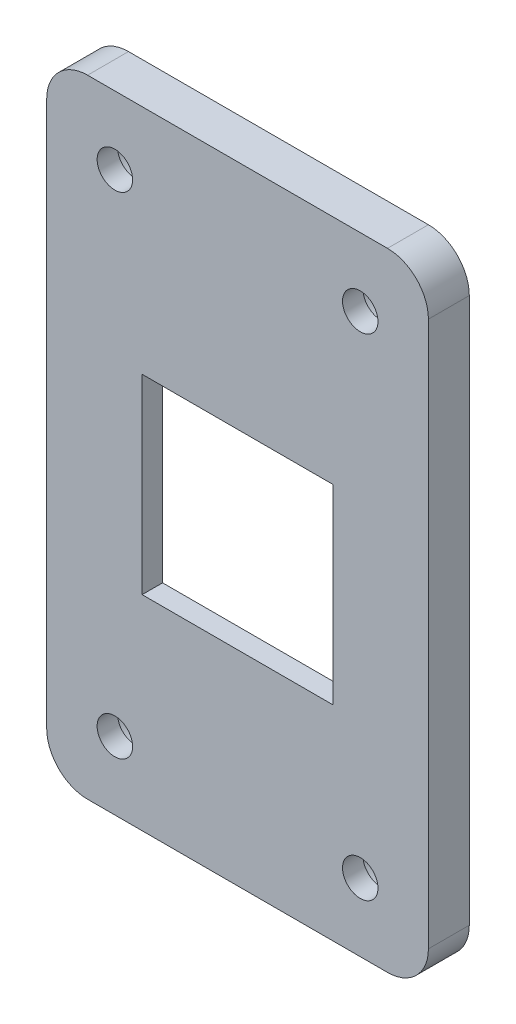
SolidWorks part; units mm, degrees
ref_plane "Front Plane" through (0, 0, 0) normal (1, 0, 0) x (0, 1, 0)
ref_plane "Top Plane" through (0, 0, 0) normal (0, 0, 1) x (0, 1, 0)
ref_plane "Right Plane" through (0, 0, 0) normal (0, 1, 0) x (-1, 0, 0)
sketch "Sketch2" plane through (0, 0, 0) normal (0, 0, 1) x (0, 1, 0)
  line L0 (-11, 10) -> (9, 10)
  line L1 (18, 9) -> (-18, 9) construction
  line L2 (18, 9) -> (18, -9) construction
  line L3 (18, -9) -> (-18, -9) construction
  line L4 (-18, 9) -> (-18, -9) construction
  line L5 (18, 9) -> (-18, -9) construction
  line L6 (18, -9) -> (-18, 9) construction
  line L7 (23, 14) -> (-23, 14)
  line L8 (23, 14) -> (23, -14)
  line L9 (23, -14) -> (-23, -14)
  line L10 (-23, 14) -> (-23, -14)
  line L11 (23, 14) -> (-23, -14) construction
  line L12 (23, -14) -> (-23, 14) construction
  line L13 (-8, 7) -> (6, 7)
  line L14 (-8, 7) -> (-8, -7)
  line L15 (-8, -7) -> (6, -7)
  line L16 (6, 7) -> (6, -7)
  line L17 (-8, 7) -> (6, -7) construction
  line L18 (-8, -7) -> (6, 7) construction
  line L19 (9, 10) -> (9, -10)
  line L20 (-11, -10) -> (9, -10)
  line L21 (-11, 10) -> (-11, -10)
  line L22 (23, 0) -> (-23, 0) construction
  circle A0 centre (-18, 9) radius 2.5
  circle A1 centre (18, 9) radius 2.5
  circle A2 centre (18, -9) radius 2.5
  circle A3 centre (-18, -9) radius 2.5
  point P0 (0, 0)
  point P6 (0, 0)
  point P16 (0, 0)
  point P26 (-1, 0)
  point P27 (0, 0)
  point P28 (0, 0)
  dimension "D5" = 5
  dimension "D1" = 36
  dimension "D2" = 18
  dimension "D3" = 5
  dimension "D4" = 5
  dimension "D6" = 14
  dimension "D8" = 1
  dimension "D7" = 3
extrude "Boss-Extrude1" add sketch "Sketch2" along normal blind 3 contours A3 | L7 L10 L9 L8 A3 A2 A1 A0 | A0 | A1 | A2 | L0 L21 L20 L19 L13 L16 L15 L14 region at (-9.7172, -1, 0) region at (0, 22.4615, 0) region at (-9, -18, 0) region at (-9, 18, 0) region at (9, 18, 0) region at (9, -18, 0)
hole_wizard "Ø2.6 (2.6) Diameter Hole1" positions "Sketch4" profile "Sketch5" hole size "Ø2.6" standard "ANSI Metric" end condition through all
sketch "Sketch4" plane through (0, 0, 0) normal (0, 0, -1) x (-1, 0, 0)
  point P0 (-9, -18)
  point P3 (9, -18)
  point P6 (-9, 18)
  point P9 (9, 18)
sketch "Sketch5" plane through (9, -18, 0) normal (1, 0, 0) x (0, 1, 0)
  line L0 (0, 0) -> (0, 3)
  line L1 (0, 3) -> (1.3, 3)
  line L2 (1.3, 3) -> (1.3, 0)
  line L5 (1.3, 0) -> (0, 0)
  line L11 (0, -6.35) -> (0, 107.95) construction
  dimension "Thru Hole Dia." = 2.6
  dimension "Thru Hole Depth" = 3
extrude "Cut-Extrude2" cut sketch "Sketch2<6>" along normal blind 1.5 contours A3 | A0 | A1 | A2 | L0 L19 L20 L21 region at (-9, -18, 0) region at (-9, 18, 0) region at (9, 18, 0) region at (9, -18, 0)
sketch "Sketch2<6>" plane through (0, 0, 0) normal (0, 0, 1) x (0, 1, 0) same geometry as "Sketch2"
fillet "Fillet1" radius 3 4 edges at (14, 23, 1.5) (14, -23, 1.5) (-14, -23, 1.5) (-14, 23, 1.5)
sketch "Sketch6" plane through (0, 0, 0) normal (0, 0, -1) x (1, 0, 0)
  line L0 (0, 15) -> (0, 13) construction
  line L1 (0.5, 15) -> (0.5, 13)
  line L2 (-0.5, 15) -> (-0.5, 13)
  line L3 (-10, 11) -> (10, 11) construction
  arc A0 (0.5, 15) -> (-0.5, 15) centre (0, 15) ccw
  arc A1 (-0.5, 13) -> (0.5, 13) centre (0, 13) ccw
  point P3 (0, 14)
  dimension "D1" = 1
  dimension "D2" = 2
  dimension "D3" = 3
extrude "Cut-Extrude3" cut sketch "Sketch6" against normal blind 0.4
equation "\"offset\"= 5"
equation "\"D4@Sketch2\"=\"offset\""
equation "\"D3@Sketch2\"=\"offset\""
